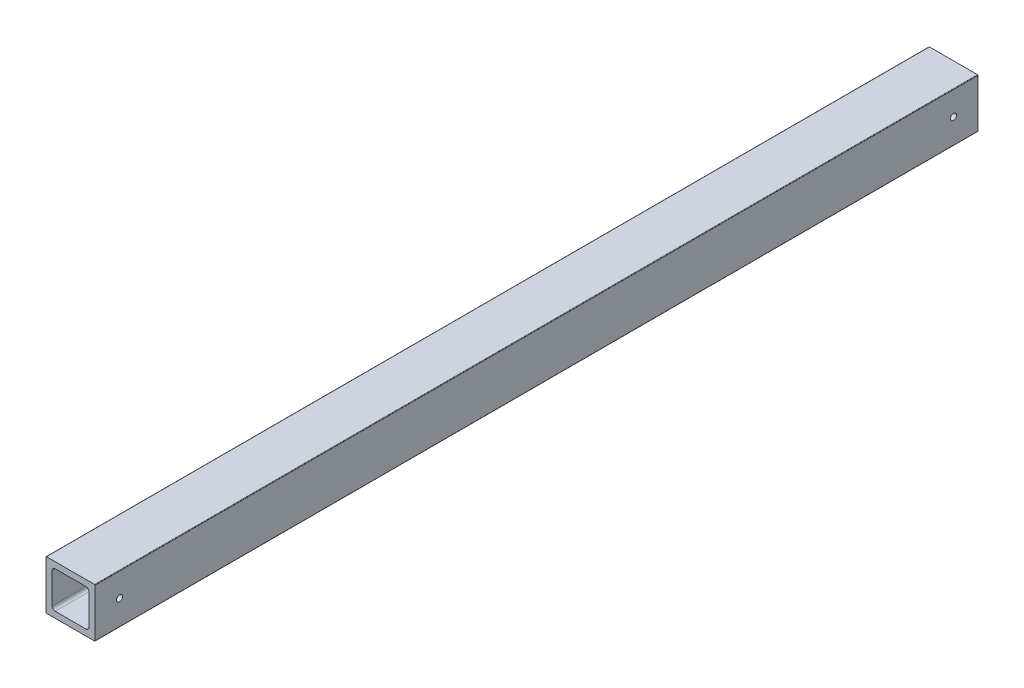
SolidWorks part; units mm, degrees
ref_plane "Front Plane" through (0, 0, 0) normal (0, 0, 1) x (1, 0, 0)
ref_plane "Top Plane" through (0, 0, 0) normal (0, 1, 0) x (1, 0, 0)
ref_plane "Right Plane" through (0, 0, 0) normal (1, 0, 0) x (0, 0, -1)
ref_plane "Plane1" through (0, 0, 0) normal (0, 0, -1) x (-1, 0, 0)
sketch "Sketch1" plane through (0, 0, 0) normal (0, 0, -1) x (-1, 0, 0)
  line L0 (-3.175, 20.6375) -> (-3.175, 4.7625)
  line L1 (-4.7625, 3.175) -> (-20.6375, 3.175)
  line L2 (-22.225, 4.7625) -> (-22.225, 20.6375)
  line L3 (-20.6375, 22.225) -> (-4.7625, 22.225)
  line L4 (0, 0.254) -> (0, 25.146)
  line L5 (-0.254, 25.4) -> (-25.146, 25.4)
  line L6 (-25.4, 25.146) -> (-25.4, 0.254)
  line L7 (-25.146, 0) -> (-0.254, 0)
  arc A0 (-3.175, 4.7625) -> (-4.7625, 3.175) centre (-4.7625, 4.7625) cw
  arc A1 (-20.6375, 3.175) -> (-22.225, 4.7625) centre (-20.6375, 4.7625) cw
  arc A2 (-22.225, 20.6375) -> (-20.6375, 22.225) centre (-20.6375, 20.6375) cw
  arc A3 (-4.7625, 22.225) -> (-3.175, 20.6375) centre (-4.7625, 20.6375) cw
  arc A4 (-0.254, 0) -> (0, 0.254) centre (-0.254, 0.254) ccw
  arc A5 (0, 25.146) -> (-0.254, 25.4) centre (-0.254, 25.146) ccw
  arc A6 (-25.146, 25.4) -> (-25.4, 25.146) centre (-25.146, 25.146) ccw
  arc A7 (-25.4, 0.254) -> (-25.146, 0) centre (-25.146, 0.254) ccw
  dimension "D1" = 25.4
  dimension "D2" = 25.4
  dimension "D3" = 19.05
  dimension "D4" = 3.175
  dimension "D5" = 19.05
extrude "Boss-Extrude1" add sketch "Sketch1" against normal blind 457.2
sketch "Sketch2" plane through (0, 0, 0) normal (-1, 0, 0) x (0, 0, 1)
  line L0 (0, 0.254) -> (0, 25.146) construction
  line L1 (457.2, 0.254) -> (0, 0.254) construction
  line L2 (457.2, 0.254) -> (457.2, 25.146) construction
  circle A0 centre (12.6975, 12.954) radius 1.5875
  circle A1 centre (444.5, 12.954) radius 1.5875
  point P4 (0, 12.7)
  dimension "D1" = 3.175
  dimension "D2" = 12.7
  dimension "D3" = 12.7
  dimension "D4" = 3.175
  dimension "D5" = 12.7
  dimension "D6" = 12.7
extrude "Cut-Extrude1" cut sketch "Sketch2" against normal through all
